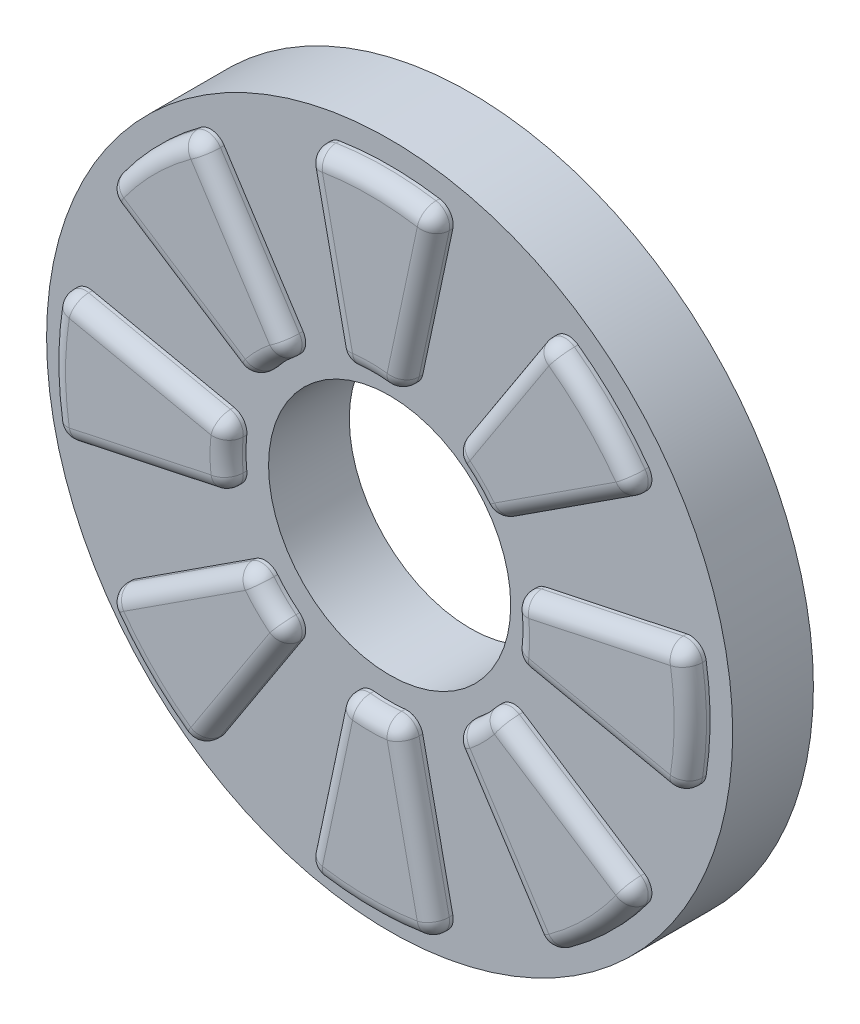
SolidWorks part; units mm, degrees
ref_plane "Front Plane" through (0, 0, 0) normal (0, 0, 1) x (1, 0, 0)
ref_plane "Top Plane" through (0, 0, 0) normal (0, 1, 0) x (1, 0, 0)
ref_plane "Right Plane" through (0, 0, 0) normal (1, 0, 0) x (0, 0, -1)
sketch "Sketch1" plane through (0, 0, 0) normal (0, 0, 1) x (1, 0, 0)
  circle A0 centre (0, 0) radius 26.9875
  circle A1 centre (0, 0) radius 9.525
  dimension "D1" = 53.975
  dimension "D2" = 19.05
extrude "Boss-Extrude1" add sketch "Sketch1" along normal blind 6.35
sketch "Sketch3" plane through (0, 0, 6.35) normal (0, 0, 1) x (1, 0, 0)
  line L0 (-5.2453, 24.6578) -> (-2.3518, 11.0556)
  line L1 (2.3518, 11.0556) -> (5.2453, 24.6578)
  line L2 (-7.8152, 24.1111) -> (-2.6753, 25.2045) construction
  line L3 (9.4805, 6.1546) -> (21.1446, 13.7267)
  line L4 (13.7267, 21.1446) -> (6.1546, 9.4805)
  line L5 (11.0556, -2.3518) -> (24.6578, -5.2453)
  line L6 (24.6578, 5.2453) -> (11.0556, 2.3518)
  line L7 (6.1546, -9.4805) -> (13.7267, -21.1446)
  line L8 (21.1446, -13.7267) -> (9.4805, -6.1546)
  line L9 (-2.3518, -11.0556) -> (-5.2453, -24.6578)
  line L10 (5.2453, -24.6578) -> (2.3518, -11.0556)
  line L11 (-9.4805, -6.1546) -> (-21.1446, -13.7267)
  line L12 (-13.7267, -21.1446) -> (-6.1546, -9.4805)
  line L13 (-11.0556, 2.3518) -> (-24.6578, 5.2453)
  line L14 (-24.6578, -5.2453) -> (-11.0556, -2.3518)
  line L15 (-6.1546, 9.4805) -> (-13.7267, 21.1446)
  line L16 (-21.1446, 13.7267) -> (-9.4805, 6.1546)
  circle A0 centre (0, 0) radius 25.2095 construction
  circle A1 centre (0, 0) radius 11.303 construction
  arc A2 (-2.3518, 11.0556) -> (2.3518, 11.0556) centre (0, 0) cw
  circle A4 centre (0, 0) radius 9.525 construction
  arc A5 (-5.2453, 24.6578) -> (5.2453, 24.6578) centre (0, 0) cw
  arc A6 (13.7267, 21.1446) -> (21.1446, 13.7267) centre (0, 0) cw
  arc A7 (6.1546, 9.4805) -> (9.4805, 6.1546) centre (0, 0) cw
  arc A8 (24.6578, 5.2453) -> (24.6578, -5.2453) centre (0, 0) cw
  arc A9 (11.0556, 2.3518) -> (11.0556, -2.3518) centre (0, 0) cw
  arc A10 (21.1446, -13.7267) -> (13.7267, -21.1446) centre (0, 0) cw
  arc A11 (9.4805, -6.1546) -> (6.1546, -9.4805) centre (0, 0) cw
  arc A12 (5.2453, -24.6578) -> (-5.2453, -24.6578) centre (0, 0) cw
  arc A13 (2.3518, -11.0556) -> (-2.3518, -11.0556) centre (0, 0) cw
  arc A14 (-13.7267, -21.1446) -> (-21.1446, -13.7267) centre (0, 0) cw
  arc A15 (-6.1546, -9.4805) -> (-9.4805, -6.1546) centre (0, 0) cw
  arc A16 (-24.6578, -5.2453) -> (-24.6578, 5.2453) centre (0, 0) cw
  arc A17 (-11.0556, -2.3518) -> (-11.0556, 2.3518) centre (0, 0) cw
  arc A18 (-21.1446, 13.7267) -> (-13.7267, 21.1446) centre (0, 0) cw
  arc A19 (-9.4805, 6.1546) -> (-6.1546, 9.4805) centre (0, 0) cw
  circle A20 centre (0, 0) radius 26.9875 construction
  point P5 (0, 11.303)
  point P8 (0, 25.2095)
  point P9 (0, 11.303)
  point P19 (-4.2593, 21.6189)
  point P21 (-5.2453, 24.6578)
  point P25 (-4.5846, 21.5523)
  dimension "D1" = 1.778
  dimension "D2" = 1.778
  dimension "D3" = 8
extrude "Boss-Extrude2" add sketch "Sketch3" along normal blind 1.5557
fillet "Fillet1" radius 1.27 32 edges at (-24.6578, 5.2453, 7.1279) (21.1446, -13.7267, 7.1279) (24.6578, 5.2453, 7.1279) (9.4805, -6.1546, 7.1279) (2.3518, -11.0556, 7.1279) (-6.1546, -9.4805, 7.1279) (-9.4805, -6.1546, 7.1279) (-11.0556, 2.3518, 7.1279) (11.0556, -2.3518, 7.1279) (24.6578, -5.2453, 7.1279) (5.2453, -24.6578, 7.1279) (-24.6578, -5.2453, 7.1279) (-11.0556, -2.3518, 7.1279) (-21.1446, -13.7267, 7.1279) (-13.7267, -21.1446, 7.1279) (-2.3518, -11.0556, 7.1279) (-5.2453, -24.6578, 7.1279) (13.7267, -21.1446, 7.1279) (6.1546, -9.4805, 7.1279) (9.4805, 6.1546, 7.1279) (11.0556, 2.3518, 7.1279) (6.1546, 9.4805, 7.1279) (21.1446, 13.7267, 7.1279) (13.7267, 21.1446, 7.1279) (-5.2453, 24.6578, 7.1279) (5.2453, 24.6578, 7.1279) (2.3518, 11.0556, 7.1279) (-2.3518, 11.0556, 7.1279) (-9.4805, 6.1546, 7.1279) (-6.1546, 9.4805, 7.1279) (-13.7267, 21.1446, 7.1279) (-21.1446, 13.7267, 7.1279)
fillet "Fillet2" radius 1.27 64 edges at (-4.7783, -24.3664, 7.9057) (-3.7883, -17.8088, 7.9057) (-2.1049, -11.4703, 7.9057) (0, -11.303, 7.9057) (2.1049, -11.4703, 7.9057) (3.7883, -17.8088, 7.9057) (4.7783, -24.3664, 7.9057) (0, -25.2095, 7.9057) (-13.8509, -20.6084, 7.9057) (-17.8258, -17.8258, 7.9057) (-20.6084, -13.8509, 7.9057) (-15.2714, -9.914, 7.9057) (-9.5991, -6.6223, 7.9057) (-7.9924, -7.9924, 7.9057) (-6.6223, -9.5991, 7.9057) (13.8509, -20.6084, 7.9057) (9.914, -15.2714, 7.9057) (6.6223, -9.5991, 7.9057) (7.9924, -7.9924, 7.9057) (9.5991, -6.6223, 7.9057) (15.2714, -9.914, 7.9057) (20.6084, -13.8509, 7.9057) (17.8258, -17.8258, 7.9057) (24.3664, -4.7783, 7.9057) (17.8088, -3.7883, 7.9057) (11.4703, -2.1049, 7.9057) (11.303, 0, 7.9057) (11.4703, 2.1049, 7.9057) (17.8088, 3.7883, 7.9057) (24.3664, 4.7783, 7.9057) (25.2095, 0, 7.9057) (6.6223, 9.5991, 7.9057) (9.914, 15.2714, 7.9057) (13.8509, 20.6084, 7.9057) (17.8258, 17.8258, 7.9057) (20.6084, 13.8509, 7.9057) (15.2714, 9.914, 7.9057) (9.5991, 6.6223, 7.9057) (7.9924, 7.9924, 7.9057) (4.7783, 24.3664, 7.9057) (3.7883, 17.8088, 7.9057) (2.1049, 11.4703, 7.9057) (0, 11.303, 7.9057) (-2.1049, 11.4703, 7.9057) (-3.7883, 17.8088, 7.9057) (-4.7783, 24.3664, 7.9057) (0, 25.2095, 7.9057) (-20.6084, 13.8509, 7.9057) (-17.8258, 17.8258, 7.9057) (-13.8509, 20.6084, 7.9057) (-9.914, 15.2714, 7.9057) (-6.6223, 9.5991, 7.9057) (-7.9924, 7.9924, 7.9057) (-9.5991, 6.6223, 7.9057) (-15.2714, 9.914, 7.9057) (-11.4703, 2.1049, 7.9057) (-11.303, 0, 7.9057) (-11.4703, -2.1049, 7.9057) (-17.8088, -3.7883, 7.9057) (-24.3664, -4.7783, 7.9057) (-25.2095, 0, 7.9057) (-24.3664, 4.7783, 7.9057) (-17.8088, 3.7883, 7.9057) (-9.914, -15.2714, 7.9057)
equation "\"D1@Chamfer1\"=1/8"
